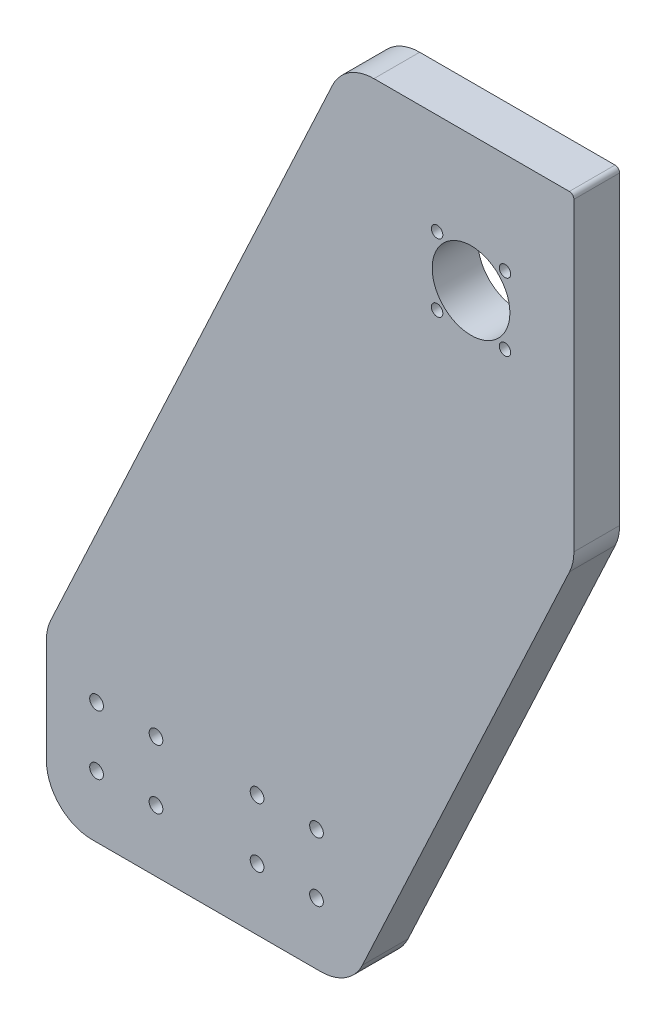
SolidWorks part; units mm, degrees
ref_plane "Piano frontale" through (0, 0, 0) normal (0, 0, 1) x (1, 0, 0)
ref_plane "Piano superiore" through (0, 0, 0) normal (0, 1, 0) x (1, 0, 0)
ref_plane "Piano destro" through (0, 0, 0) normal (1, 0, 0) x (0, 0, -1)
sketch "Schizzo1" plane through (0, 0, 0) normal (0, 0, 1) x (1, 0, 0)
  line L0 (20, 0) -> (120.1237, 0)
  line L1 (138.2499, 11.5476) -> (228.9159, 205.9815)
  line L2 (230.7898, 214.4339) -> (230.7898, 348)
  line L3 (228.7898, 350) -> (143.3075, 350)
  line L4 (0, 65.5661) -> (0, 20)
  line L5 (125.1814, 338.4524) -> (1.8738, 74.0185)
  line L6 (236.5641, 399.8483) -> (-0.2256, -107.9489) construction
  line L7 (0, 40) -> (151.5175, 40) construction
  line L8 (105.1756, 40) -> (105.1756, 85.084) construction
  line L9 (185.7898, 290.9623) -> (170.9405, 305.8115) construction
  line L10 (185.7898, 290.9623) -> (164.7898, 290.9623) construction
  line L11 (185.7898, 290.9623) -> (185.7898, 311.9623) construction
  line L12 (70.0619, 0) -> (70.0619, 220.2482) construction
  line L19 (34.9482, 40) -> (34.9482, 85.084) construction
  line L20 (140.1237, 40) -> (-11.3937, 40) construction
  circle A0 centre (92.1756, 53) radius 3
  circle A1 centre (118.1756, 53) radius 3
  circle A2 centre (118.1756, 27) radius 3
  circle A3 centre (92.1756, 27) radius 3
  circle A4 centre (185.7898, 290.9623) radius 17
  circle A5 centre (185.7898, 290.9623) radius 21 construction
  arc A6 (138.2499, 11.5476) -> (120.1237, 0) centre (120.1237, 20) cw
  arc A7 (20, 0) -> (0, 20) centre (20, 20) cw
  arc A8 (0, 65.5661) -> (1.8738, 74.0185) centre (20, 65.5661) cw
  arc A9 (230.7898, 214.4339) -> (228.9159, 205.9815) centre (210.7898, 214.4339) cw
  arc A10 (230.7898, 348) -> (228.7898, 350) centre (228.7898, 348) ccw
  arc A11 (143.3075, 350) -> (125.1814, 338.4524) centre (143.3075, 330) ccw
  circle A14 centre (200.639, 305.8115) radius 2.5
  circle A15 centre (200.639, 276.1131) radius 2.5
  circle A18 centre (170.9405, 276.1131) radius 2.5
  circle A19 centre (170.9405, 305.8115) radius 2.5
  circle A20 centre (47.9482, 27) radius 3
  circle A21 centre (21.9482, 27) radius 3
  circle A22 centre (21.9482, 53) radius 3
  circle A23 centre (47.9482, 53) radius 3
  point P27 (170.9405, 305.8115)
  point P28 (200.639, 305.8115)
  point P29 (200.639, 276.1131)
  point P30 (170.9405, 276.1131)
  point P31 (230.7898, 350)
  point P39 (0, 0)
  point P42 (0, 70)
  point P45 (230.7898, 210)
  point P48 (230.7898, 350)
  dimension "D6" = 6
  dimension "D7" = 13
  dimension "D9" = 34
  dimension "D11" = 45
  dimension "D14" = 20
  dimension "D15" = 5
  dimension "D16" = 40
  dimension "D17" = 42
  dimension "D12" = 2
  dimension "D1" = 115
  dimension "D2" = 150
  dimension "D3" = 70
  dimension "D4" = 350
  dimension "D5" = 140
  dimension "D8" = 13
  dimension "D10" = 45
  dimension "D18" = 33
extrude "Estrusione-Estrusione2" add sketch "Schizzo1" against normal blind 20
sketch "Schizzo2" plane through (0, 0, 0) normal (0, -1, 0) x (1, 0, 0)
  line L0 (20, -10) -> (120.1237, -10) construction
  line L1 (20, -20) -> (20, 0) construction
  line L2 (120.1237, -20) -> (120.1237, 0) construction
  line L3 (70.0619, -10) -> (70.0619, 0) construction
  line L4 (20, 0) -> (120.1237, 0) construction
  circle A0 centre (70.0619, -10) radius 2
  circle A1 centre (97.5619, -10) radius 2
  circle A2 centre (42.5619, -10) radius 2
  dimension "D1" = 4
  dimension "D2" = 27.5
extrude "Taglio-Estrusione1" cut sketch "Schizzo2" against normal blind 15
